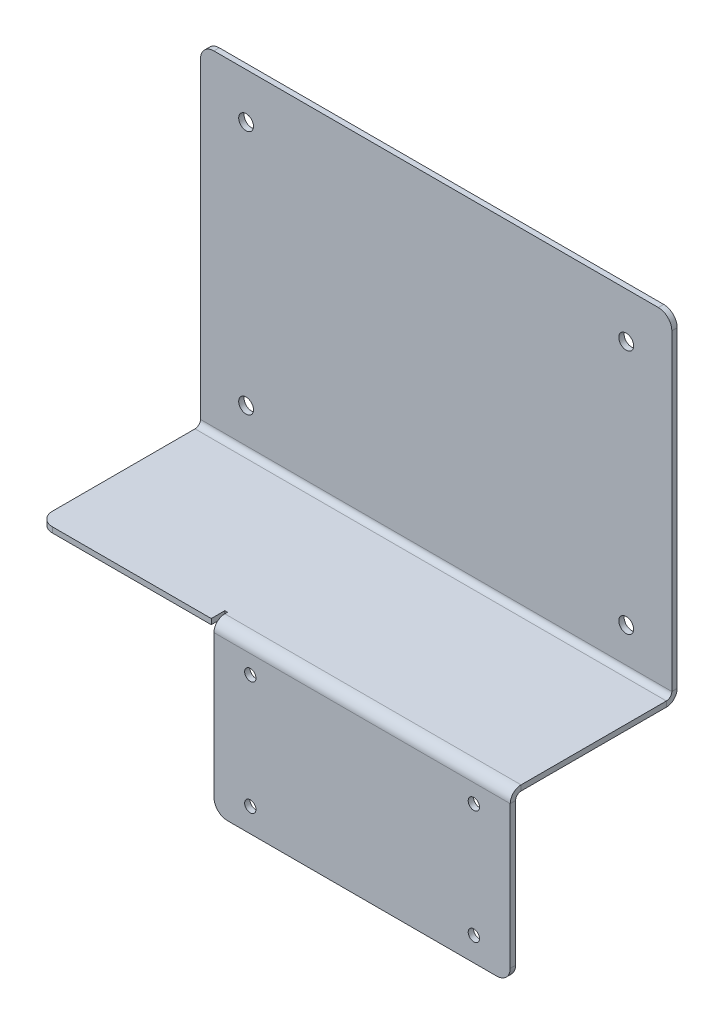
SolidWorks part; units mm, degrees
note: The reader was unsure of these and kept them because the rebuilt part matched: flange length of "Edge-Flange1", "Edge-Flange3".
ref_plane "Front Plane" through (0, 0, 0) normal (0, 0, 1) x (1, 0, 0)
ref_plane "Top Plane" through (0, 0, 0) normal (0, 1, 0) x (1, 0, 0)
ref_plane "Right Plane" through (0, 0, 0) normal (1, 0, 0) x (0, 0, -1)
sketch "Sketch1" plane through (0, 0, 0) normal (0, 0, 1) x (1, 0, 0)
  line L0 (87.5, 62.5) -> (87.5, -62.5)
  line L1 (87.5, -62.5) -> (-87.5, -62.5)
  line L2 (-87.5, 62.5) -> (87.5, 62.5)
  line L3 (-87.5, 62.5) -> (-87.5, -62.5)
  circle A0 centre (70.5634, 45.5634) radius 2.75
  circle A1 centre (70.5634, -45.5634) radius 2.75
  circle A2 centre (-70.5634, 45.5634) radius 2.75
  circle A3 centre (-70.5634, -45.5634) radius 2.75
base flange "Base-Flange1" sketch "Sketch1" thickness 2 reverse thickness direction yes parameters "D1"=8
edge flange "Edge-Flange1" sketch "Sketch10" flange angle 90 flange length 62 flange position material inside bend radius 2.03 thickness 2 relief rectangular parameters "D6"=10
sketch "Sketch10" plane through (0, -62.5, 2) normal (0, 1, 0) x (-1, 0, 0)
  line L2 (-87.5, 0) -> (-87.5, 60)
  line L3 (-87.5, 60) -> (87.5, 60)
  line L4 (87.5, 60) -> (87.5, 0)
  line L5 (87.5, 0) -> (-87.5, 0) construction
  line L6 (87.5, 0) -> (-87.5, 0)
bend "EdgeBend1" bend radius 2.03 bend angle 90 parameters "D5"=1
edge flange "Edge-Flange3" sketch "Sketch17" flange angle 90 flange length 62 flange position material inside bend radius 2.03 thickness 2 relief rectangular parameters "D6"=10
sketch "Sketch17" plane through (0, -62.5, 62) normal (0, 0, -1) x (1, 0, 0)
  line L2 (-22.5, 0) -> (-22.5, 60)
  line L3 (-22.5, 60) -> (87.5, 60)
  line L4 (87.5, 60) -> (87.5, 0)
  line L5 (87.5, 0) -> (-87.5, 0) construction
  line L6 (87.5, 0) -> (-22.5, 0)
  dimension "D1" = 110
bend "EdgeBend3" bend radius 2.03 bend angle 90 parameters "D5"=2
sketch "Sketch18" plane through (0, 0, 62) normal (0, 0, 1) x (1, 0, 0)
  circle A0 centre (-9, -71.3727) radius 2.1
  circle A1 centre (-9, -113.6273) radius 2.1
  circle A2 centre (74, -71.3727) radius 2.1
  circle A3 centre (74, -113.6273) radius 2.1
extrude "Cut-Extrude2" cut sketch "Sketch18" against normal up to next normal cut yes
fillet "Fillet1" radius 5 5 edges at (87.5, -122.5, 61) (-22.5, -122.5, 61) (-87.5, -61.5, 62) (87.5, 62.5, 1) (-87.5, 62.5, 1)
sketch "Bend-Lines1" [suppressed] plane through (0, 0, 0) normal (0, 1, 0) x (1, 0, 0)
sketch "Bounding-Box1" [suppressed] plane through (0, 0, 0) normal (0, 1, 0) x (1, 0, 0)
sheet metal parameters "Sheet-Metal1" thickness 2 parameters "D1"=8
flat pattern "Flat-Pattern1" [suppressed]
sketch "Bend-Lines2" plane through (0, 0, 0) normal (0, 1, 0) x (1, 0, 0)
sketch3d "Bounding-Box2" [suppressed]
  line L0 (-87.5, -62.5, 0) -> (87.5, -62.5, 0) construction
  line L1 (-87.5, 62.5, 0) -> (87.5, 62.5, 0) construction
  line L2 (-87.5, -62.5, 0) -> (-87.5, 62.5, 0) construction
  line L3 (87.5, -62.5, 0) -> (87.5, 62.5, 0) construction
sheet metal parameters "Sheet-Metal2" thickness 2 parameters "D1"=8
flat pattern "Flat-Pattern1"
sketch "Bend-Lines2" plane through (0, 0, 0) normal (0, 0, -1) x (-1, 0, 0)
  line L0 (-87.5, -60.8498) -> (87.5, -60.8498) construction
  line L1 (-87.5, -60.8498) -> (87.5, -60.8498) construction
sketch3d "Bounding-Box2" [suppressed]
  line L0 (-87.5, 62.5, 0) -> (-87.5, -121.1995, 0) construction
  line L1 (87.5, 62.5, 0) -> (87.5, -121.1995, 0) construction
  line L2 (-87.5, 62.5, 0) -> (87.5, 62.5, 0) construction
  line L3 (-87.5, -121.1995, 0) -> (87.5, -121.1995, 0) construction
bend of the flat pattern "Flatten-<EdgeBend1>1"
sheet metal parameters "Sheet-Metal5" thickness 2 parameters "D1"=8
flat pattern "Flat-Pattern1"
sketch "Bend-Lines2" plane through (0, 0, 0) normal (0, 0, -1) x (-1, 0, 0)
  line L0 (-87.5, -60.8498) -> (87.5, -60.8498) construction
  line L1 (-87.5, -60.8498) -> (87.5, -60.8498) construction
  line L2 (-87.5, -119.5493) -> (22.5, -119.5493) construction
  line L3 (-87.5, -119.5493) -> (22.5, -119.5493) construction
sketch3d "Bounding-Box2" [suppressed]
  line L0 (-87.5, 62.5, 0) -> (-87.5, -179.899, 0) construction
  line L1 (87.5, 62.5, 0) -> (87.5, -179.899, 0) construction
  line L2 (-87.5, 62.5, 0) -> (87.5, 62.5, 0) construction
  line L3 (-87.5, -179.899, 0) -> (87.5, -179.899, 0) construction
bend of the flat pattern "Flatten-<EdgeBend1>1"
bend of the flat pattern "Flatten-<EdgeBend3>1"
sheet metal parameters "Sheet-Metal6" thickness 2 parameters "D1"=8
flat pattern "Flat-Pattern1"
sketch "Bend-Lines2" plane through (0, 0, 0) normal (0, 0, -1) x (-1, 0, 0)
  line L0 (-87.5, -60.8498) -> (87.5, -60.8498) construction
  line L1 (-87.5, -60.8498) -> (87.5, -60.8498) construction
  line L2 (-87.5, -119.5493) -> (22.5, -119.5493) construction
  line L3 (-87.5, -119.5493) -> (22.5, -119.5493) construction
sketch3d "Bounding-Box2" [suppressed]
  line L0 (-87.4999, -179.899, 0) -> (-87.5, 62.5, 0) construction
  line L1 (87.5, -179.8989, 0) -> (87.4999, 62.5001, 0) construction
  line L2 (-87.4999, -179.899, 0) -> (87.5, -179.8989, 0) construction
  line L3 (-87.5, 62.5, 0) -> (87.4999, 62.5001, 0) construction
bend of the flat pattern "Flatten-<EdgeBend1>1"
bend of the flat pattern "Flatten-<EdgeBend3>1"
